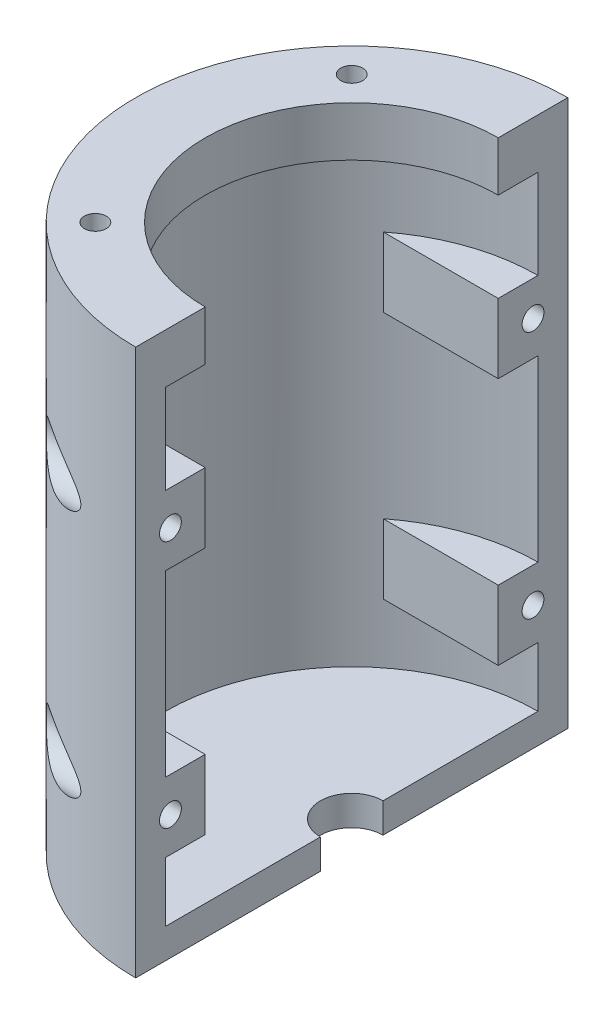
SolidWorks part; units mm, degrees
ref_plane "正面" through (0, 0, 0) normal (0, 0, 1) x (1, 0, 0)
ref_plane "平面" through (0, 0, 0) normal (0, 1, 0) x (1, 0, 0)
ref_plane "右側面" through (0, 0, 0) normal (1, 0, 0) x (0, 0, -1)
sketch "ｽｹｯﾁ1" plane through (0, 0, 0) normal (0, 1, 0) x (1, 0, 0)
  line L0 (0, -21.75) -> (0, -14.75)
  line L1 (0, -14.75) -> (0, 14.75) construction
  line L2 (0, 14.75) -> (0, 21.75)
  arc A0 (0, 21.75) -> (0, -21.75) centre (0, 0) ccw
  arc A1 (0, 14.75) -> (0, -14.75) centre (0, 0) ccw
  dimension "D1" = 14.75
  dimension "D2" = 7
extrude "ﾎﾞｽ - 押し出し1" add sketch "ｽｹｯﾁ1" along normal blind 55
sketch "ｽｹｯﾁ2" plane through (0, 55, 0) normal (0, 1, 0) x (1, 0, 0)
  circle A0 centre (0, 0) radius 14.75
  circle A1 centre (0, 0) radius 18.75
  arc A2 (0, 14.75) -> (0, -14.75) centre (0, 0) ccw construction
  arc A3 (0, 21.75) -> (0, -21.75) centre (0, 0) ccw construction
  dimension "D1" = 3
extrude "ｶｯﾄ - 押し出し1" cut sketch "ｽｹｯﾁ2" against normal through all from offset 5 offset against normal yes
sketch "ｽｹｯﾁ4" plane through (0, 0, 0) normal (1, 0, 0) x (0, 0, -1)
  line L0 (-14.75, 12.5) -> (-21.75, 12.5) construction
  line L1 (-21.75, 41) -> (-21.75, 34)
  line L2 (-18.75, 50) -> (-14.75, 50) construction
  line L3 (21.75, 55) -> (21.75, 0) construction
  line L4 (18.75, 50) -> (18.75, 0) construction
  line L5 (-21.75, 16) -> (-14.75, 16)
  line L6 (-14.75, 16) -> (-14.75, 9)
  line L7 (-14.75, 9) -> (-21.75, 9)
  line L8 (-21.75, 9) -> (-21.75, 16)
  line L9 (-21.75, 50) -> (21.75, 50) construction
  line L10 (0, 25) -> (-21.75, 25) construction
  line L11 (0, 25) -> (21.75, 25) construction
  line L12 (-21.75, 37.5) -> (21.75, 37.5) construction
  line L13 (-21.75, 0) -> (21.75, 0) construction
  line L14 (0, 50) -> (0, 0) construction
  line L15 (-18.25, 50) -> (-18.25, 0) construction
  line L16 (18.75, 50) -> (18.75, 37.5) construction
  line L17 (18.75, 37.5) -> (18.75, 25) construction
  line L18 (-21.75, 55) -> (-21.75, 0) construction
  line L19 (-21.75, 34) -> (-14.75, 34)
  line L20 (-14.75, 34) -> (-14.75, 41)
  line L21 (-14.75, 41) -> (-21.75, 41)
  line L22 (21.75, 9) -> (21.75, 16)
  line L23 (21.75, 16) -> (14.75, 16)
  line L24 (14.75, 16) -> (14.75, 9)
  line L25 (14.75, 9) -> (21.75, 9)
  line L26 (21.75, 34) -> (14.75, 34)
  line L27 (21.75, 41) -> (21.75, 34)
  line L28 (14.75, 41) -> (21.75, 41)
  line L29 (14.75, 34) -> (14.75, 41)
  circle A0 centre (-18.25, 37.5) radius 1.1 construction
  circle A1 centre (18.25, 37.5) radius 1.1 construction
  circle A2 centre (18.25, 12.5) radius 1.1 construction
  circle A3 centre (-18.25, 12.5) radius 1.1 construction
  dimension "D1" = 2.2
  dimension "D2" = 3.5
  dimension "D3" = 7
  dimension "D4" = 7
extrude "ﾎﾞｽ - 押し出し3" add sketch "ｽｹｯﾁ4" against normal up to next
sketch "ｽｹｯﾁ3" plane through (0, 0, 0) normal (1, 0, 0) x (0, 0, -1)
  line L0 (-21.75, 50) -> (21.75, 50) construction
  line L1 (0, 25) -> (-21.75, 25) construction
  line L2 (0, 25) -> (21.75, 25) construction
  line L3 (-21.75, 55) -> (-21.75, 0) construction
  line L4 (-21.75, 37.5) -> (21.75, 37.5) construction
  line L5 (21.75, 55) -> (21.75, 0) construction
  line L6 (-21.75, 0) -> (21.75, 0) construction
  line L7 (0, 50) -> (0, 0) construction
  line L8 (14.75, 50) -> (18.75, 50) construction
  line L9 (-18.25, 50) -> (-18.25, 0) construction
  line L10 (18.75, 50) -> (18.75, 37.5) construction
  line L11 (18.75, 37.5) -> (18.75, 25) construction
  line L12 (18.75, 50) -> (18.75, 41) construction
  circle A0 centre (-18.25, 37.5) radius 1.1
  circle A1 centre (18.25, 37.5) radius 1.1
  circle A2 centre (18.25, 12.5) radius 1.1
  circle A3 centre (-18.25, 12.5) radius 1.1
  dimension "D1" = 2.2
  dimension "D2" = 3.5
extrude "ｶｯﾄ - 押し出し2" cut sketch "ｽｹｯﾁ3" against normal blind 5
sketch "ｽｹｯﾁ5" plane through (0, 0, 0) normal (1, 0, 0) x (0, 0, -1)
  circle A0 centre (-18.25, 37.5) radius 2.5
  circle A1 centre (-18.25, 12.5) radius 2.5
  circle A2 centre (18.25, 12.5) radius 2.5
  circle A3 centre (18.25, 37.5) radius 2.5
  dimension "D1" = 5
extrude "ｶｯﾄ - 押し出し3" cut sketch "ｽｹｯﾁ5" against normal through all from offset 4 offset against normal yes
sketch "ｽｹｯﾁ6" plane through (0, 55, 0) normal (0, 1, 0) x (1, 0, 0)
  line L0 (0, 0) -> (-14.75, 0) construction
  line L1 (-14.75, 0) -> (-18.25, 0) construction
  line L2 (-18.25, 0) -> (-21.75, 0) construction
  line L3 (0, 0) -> (-12.9047, -12.9047) construction
  line L4 (-12.9047, 12.9047) -> (0, 0) construction
  circle A0 centre (0, 0) radius 18.25 construction
  arc A1 (0, 14.75) -> (0, -14.75) centre (0, 0) ccw construction
  arc A2 (0, 21.75) -> (0, -21.75) centre (0, 0) ccw construction
  circle A3 centre (-12.9047, -12.9047) radius 1.1
  circle A4 centre (-12.9047, 12.9047) radius 1.1
  dimension "D2" = 2.2
  dimension "D1" = 45
  dimension "D4" = 90
  dimension "D3" = 2
extrude "ｶｯﾄ - 押し出し4" cut sketch "ｽｹｯﾁ6" against normal up to vertex (5 mm away) up to point (0, 50, -14.75)
sketch "ｽｹｯﾁ7" plane through (0, 0, 0) normal (0, -1, 0) x (1, 0, 0)
  line L0 (0, -18.75) -> (0, -21.75) construction
  line L1 (0, -18.75) -> (0, 18.75) construction
  line L2 (0, -3.15) -> (0, -18.75)
  line L3 (0, 3.15) -> (0, 18.75)
  arc A0 (0, 18.75) -> (0, -18.75) centre (0, 0) ccw
  arc A1 (0, 3.15) -> (0, -3.15) centre (0, 0) ccw
  dimension "D1" = 3.15
extrude "ﾎﾞｽ - 押し出し4" add sketch "ｽｹｯﾁ7" against normal blind 3
